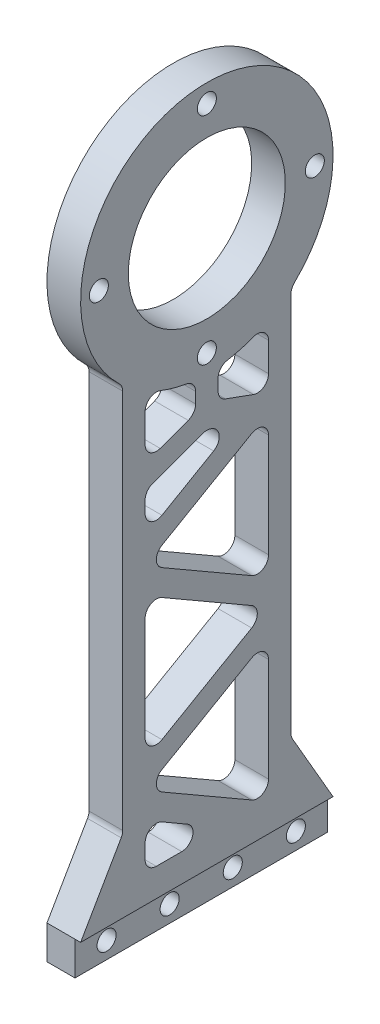
SolidWorks part; units mm, degrees
material "Сплав 2024"
ref_plane "Спереди" through (0, 0, 0) normal (0, 0, 1) x (1, 0, 0)
ref_plane "Сверху" through (0, 0, 0) normal (0, 1, 0) x (1, 0, 0)
ref_plane "Справа" through (0, 0, 0) normal (1, 0, 0) x (0, 0, -1)
sketch "Эскиз1" plane through (0, 0, 0) normal (0, 1, 0) x (1, 0, 0)
  line L1 (0, 0) -> (6, 0)
  line L2 (0, 0) -> (0, -30)
  line L3 (0, -30) -> (6, -30)
  line L4 (6, 0) -> (6, -30)
  dimension "D1" = 6
  dimension "D2" = 30
extrude "Бобышка-Вытянуть1" add sketch "Эскиз1" along normal blind 227
sketch "Эскиз2" plane through (0, 0, 0) normal (-1, 0, 0) x (0, 0, 1)
  line L0 (30, 105) -> (0, 105) construction
  line L3 (15, 227) -> (15, 0) construction
  line L4 (0, 227) -> (30, 227) construction
  line L5 (0, 0) -> (30, 0) construction
  line L6 (30, 0) -> (0, 0) construction
  circle A0 centre (15, 105) radius 22.5
  dimension "D1" = 45
  dimension "D2" = 105
extrude "Бобышка-Вытянуть2" add sketch "Эскиз2" against normal up to surface (6 mm away) up to face at (6, 113.5, 15)
sketch "Эскиз3" plane through (0, 0, 0) normal (-1, 0, 0) x (0, 0, 1)
  circle A0 centre (15, 105) radius 14
  dimension "D1" = 28
extrude "Вырез-Вытянуть1" cut sketch "Эскиз3" against normal through all
sketch "Эскиз4" plane through (6, 0, 0) normal (-1, 0, 0) x (0, 0, 1)
  line L0 (15, 127.5) -> (15, 82.5) construction
  line L1 (15, 227) -> (15, 0) construction
  line L2 (37.5, 105) -> (-7.5, 105) construction
  circle A0 centre (15, 105) radius 19.25 construction
  circle A1 centre (15, 105) radius 22.5 construction
  dimension "D1" = 38.5
hole_wizard "Отверстие с зазором M32" positions "Эскиз6" profile "Эскиз5" hole size "M3" standard "Ansi Metric" end condition through all
sketch "Эскиз6" plane through (6, -25.0247, 7.2629) normal (-1, 0, 0) x (0, 0, 1)
  line L0 (7.7371, 152.5247) -> (7.7371, 107.5247) construction
  line L1 (30.2371, 130.0247) -> (-14.7629, 130.0247) construction
  circle A0 centre (7.7371, 130.0247) radius 19.25 construction
  point P0 (7.7371, 149.2747)
  point P6 (-11.5129, 130.0247)
  point P10 (7.7371, 110.7747)
  point P12 (26.9871, 130.0247)
sketch "Эскиз5" plane through (6, 124.25, 15) normal (0, 1, 0) x (0, 0, -1)
  line L0 (0, 0) -> (0, 6)
  line L1 (0, 6) -> (1.7, 6)
  line L2 (1.7, 6) -> (1.7, 0)
  line L5 (1.7, 0) -> (0, 0)
  line L11 (0, -6.35) -> (0, 107.95) construction
  dimension "Диаметр сквозного отверстия" = 3.4
  dimension "Глубина сквозного отверстия" = 6
sketch "Эскиз8" plane through (6, 0, 0) normal (1, 0, 0) x (0, 0, -1)
  line L0 (-15, 227) -> (-15, 0) construction
  line L1 (-30, 227) -> (0, 227) construction
  line L2 (-30, 0) -> (0, 0) construction
  line L3 (19.447, 105) -> (-49.447, 105) construction
  line L4 (0, 227) -> (0, 121.7705) construction
  line L5 (-26, 145) -> (-4, 145) construction
  line L6 (-26, 145) -> (-26, 65) construction
  line L7 (-26, 65) -> (-4, 65) construction
  line L8 (-4, 145) -> (-4, 65) construction
  line L9 (-26, 145) -> (-4, 65) construction
  line L10 (-26, 65) -> (-4, 145) construction
  point P8 (-15, 105)
  point P9 (-15, 105)
  dimension "D1" = 4
  dimension "D2" = 80
  dimension "D3" = 105
sketch "Эскиз11" plane through (6, 0, 0) normal (1, 0, 0) x (0, 0, -1)
  line L0 (-30, 0) -> (0, 0) construction
  line L1 (-15, 227) -> (-15, 0) construction
  line L2 (-30, 227) -> (0, 227) construction
  line L3 (0, 88.2295) -> (0, 0) construction
  line L4 (-30, 88.2295) -> (-30, 0) construction
  line L5 (-37.5, 3) -> (7.5, 3) construction
  line L6 (-9.375, 6) -> (-9.375, 0) construction
  line L7 (-3.75, 6) -> (-3.75, 0) construction
  line L8 (1.875, 6) -> (1.875, 0) construction
  line L20 (-15, 0) -> (-15, 6) construction
  line L21 (-20.625, 0) -> (-20.625, 6) construction
  line L22 (-26.25, 0) -> (-26.25, 6) construction
  line L23 (-31.875, 0) -> (-31.875, 6) construction
  line L25 (-37.5, 0) -> (7.5, 6) construction
  line L26 (-37.5, 6) -> (7.5, 0) construction
  line L27 (-37.5, 6) -> (7.5, 6) construction
  line L28 (0, 18.9904) -> (7.5, 6)
  line L29 (-30, 18.9904) -> (0, 18.9904)
  line L30 (7.5, 6) -> (7.5, 0)
  line L31 (-37.5, 0) -> (7.5, 0)
  line L32 (-37.5, 6) -> (-37.5, 0)
  line L33 (-37.5, 6) -> (-30, 18.9904)
  point P2 (-15, 3)
  dimension "D1" = 45
  dimension "D2" = 6
  dimension "D3" = 5.625
  dimension "D4" = 5.625
  dimension "D5" = 5.625
  dimension "D6" = 5.625
  dimension "D7" = 120
  dimension "D8" = 5.625
  dimension "D9" = 5.625
  dimension "D10" = 5.625
extrude "Бобышка-Вытянуть3" add sketch "Эскиз11" against normal up to surface (6 mm away) up to face at (0, 124.25, 13.3)
hole_wizard "Отверстие с зазором M31" positions "Эскиз13" profile "Эскиз12" hole size "M3" standard "Ansi Metric" end condition through all
sketch "Эскиз13" plane through (6, 0, 0) normal (1, 0, 0) x (0, 0, -1)
  line L4 (-31.875, 0) -> (-31.875, 6) construction
  line L8 (1.875, 6) -> (1.875, 0) construction
  line L9 (-9.375, 6) -> (-9.375, 0) construction
  line L10 (-20.625, 0) -> (-20.625, 6) construction
  point P16 (-31.875, 3)
  point P20 (-20.625, 3)
  point P24 (-9.375, 3)
  point P28 (1.875, 3)
sketch "Эскиз12" plane through (6, 3, 31.875) normal (0, 1, 0) x (0, 0, -1)
  line L0 (0, 0) -> (0, 6)
  line L1 (0, 6) -> (1.7, 6)
  line L2 (1.7, 6) -> (1.7, 0)
  line L5 (1.7, 0) -> (0, 0)
  line L11 (0, -6.35) -> (0, 107.95) construction
  dimension "Диаметр сквозного отверстия" = 3.4
  dimension "Глубина сквозного отверстия" = 6
sketch "Эскиз14" plane through (6, 0, 0) normal (1, 0, 0) x (0, 0, -1)
  line L5 (-37.5, 0) -> (7.5, 0)
  line L6 (-37.5, 0) -> (-37.5, 6)
  line L7 (-37.5, 6) -> (7.5, 6)
  line L8 (7.5, 0) -> (7.5, 6)
extrude "Вырез-Вытянуть2" cut sketch "Эскиз14" against normal blind 1
sketch "Эскиз15" plane through (6, 0, 0) normal (1, 0, 0) x (0, 0, -1)
  line L0 (0, 227) -> (0, 121.7705) construction
  line L1 (-30, 227) -> (0, 227)
  line L2 (-30, 227) -> (-30, 121.7705)
  line L4 (0, 227) -> (0, 121.7705)
  arc A1 (-30, 121.7705) -> (0, 121.7705) centre (-15, 105) cw
extrude "Вырез-Вытянуть3" cut sketch "Эскиз15" against normal up to surface (6 mm away) up to face at (0, 3, 30.175)
sketch "Эскиз16" [suppressed] plane through (6, 0, 0) normal (1, 0, 0) x (0, 0, -1)
  line L0 (-26, 0) -> (-26, 89.3005) construction
  line L1 (-37.5, 0) -> (7.5, 0) construction
  line L2 (-4, 0) -> (-4, 89.3005) construction
  line L3 (-30, 88.2295) -> (-30, 18.9904) construction
  line L4 (0, 88.2295) -> (0, 18.9904) construction
  line L5 (-30, 80.25) -> (0, 80.25) construction
  line L6 (-26, 80.25) -> (-4, 80.25)
  line L7 (-4, 80.25) -> (-26, 67.5483)
  line L8 (-26, 67.5483) -> (-26, 80.25)
  line L9 (-26, 62.9295) -> (-4, 75.6312)
  line L10 (-4, 75.6312) -> (-4, 50.2278)
  line L11 (-4, 50.2278) -> (-26, 62.9295)
  line L12 (-26, 58.3107) -> (-4, 45.609)
  line L13 (-4, 45.609) -> (-26, 32.9073)
  line L14 (-26, 32.9073) -> (-26, 58.3107)
  line L15 (-26, 28.2885) -> (-4, 40.9902)
  line L16 (-4, 40.9902) -> (-4, 15.5868)
  line L17 (-4, 15.5868) -> (-26, 28.2885)
  line L18 (-26, 23.6697) -> (-4, 10.968)
  line L19 (-4, 10.968) -> (-26, 10.968)
  line L20 (-26, 10.968) -> (-26, 23.6697)
  circle A2 centre (-15, 85.75) radius 1.7 construction
  dimension "D3" = 5.5
  dimension "D1" = 4
  dimension "D2" = 4
  dimension "D4" = 30
  dimension "D5" = 4
  dimension "D6" = 4
  dimension "D7" = 4
  dimension "D8" = 4
  dimension "D9" = 60
  dimension "D10" = 60
  dimension "D11" = 60
extrude "Вырез-Вытянуть4" [suppressed] cut sketch "Эскиз16" against normal through all
fillet "Скругление1" [suppressed] radius 2
chamfer "Фаска1" [suppressed] distance 1 angle 45
sketch "Эскиз17" plane through (6, 0, 0) normal (1, 0, 0) x (0, 0, -1)
  line L0 (-26, 0) -> (-26, 111.7401) construction
  line L1 (-37.5, 0) -> (7.5, 0) construction
  line L2 (-4, 0) -> (-4, 111.7401) construction
  line L3 (-30, 88.2295) -> (-30, 18.9904) construction
  line L4 (0, 88.2295) -> (0, 18.9904) construction
  line L5 (-17, 82.5891) -> (-17, 77.4791)
  line L6 (-13, 82.5891) -> (-13, 77.4791)
  line L7 (-15, 227) -> (-15, 0) construction
  line L8 (-17, 77.4791) -> (-26, 74.2033)
  line L9 (-30, 74.2033) -> (0, 74.2033) construction
  line L10 (-13, 77.4791) -> (-4, 74.2033)
  line L11 (-26, 85.3722) -> (-26, 74.2033)
  line L12 (-30, 77.4791) -> (0, 77.4791) construction
  line L13 (-4, 74.2033) -> (-4, 85.3722)
  line L14 (-26, 69.9466) -> (-15, 73.9503)
  line L15 (-15, 73.9503) -> (-10.073, 72.157)
  line L16 (-4, 71.0444) -> (-4, 45.641)
  line L17 (-26, 69.9466) -> (-26, 62.9615)
  line L18 (-26, 53.7239) -> (-4, 41.0222)
  line L19 (-4, 41.0222) -> (-26, 28.3205)
  line L20 (-26, 28.3205) -> (-26, 53.7239)
  line L21 (-26, 23.7017) -> (-4, 36.4034)
  line L22 (-4, 36.4034) -> (-4, 11)
  line L23 (-4, 11) -> (-26, 23.7017)
  line L24 (-26, 19.0829) -> (-12, 11)
  line L25 (-12, 11) -> (-26, 11)
  line L26 (-26, 11) -> (-26, 19.0829)
  line L27 (-34.6132, 11) -> (4.6132, 11) construction
  line L28 (-30, 18.9904) -> (-37.5, 6) construction
  line L29 (7.5, 6) -> (0, 18.9904) construction
  line L30 (7.5, 6) -> (-37.5, 6) construction
  line L31 (-26, 58.3427) -> (-4, 45.641)
  line L32 (-26, 58.3427) -> (-4, 71.0444) construction
  line L33 (-26, 62.9615) -> (-10.073, 72.157) construction
  line L35 (-26, 58.3427) -> (-4, 71.0444)
  line L36 (-10.073, 72.157) -> (-26, 62.9615)
  circle A0 centre (-15, 105) radius 22.5 construction
  arc A1 (-26, 85.3722) -> (-17, 82.5891) centre (-15, 105) ccw
  arc A2 (-13, 82.5891) -> (-4, 85.3722) centre (-15, 105) ccw
  point P10 (-26, 85.3722)
  point P11 (-4, 85.3722)
  dimension "D1" = 4
  dimension "D2" = 4
  dimension "D3" = 4
  dimension "D4" = 2
  dimension "D5" = 4
  dimension "D6" = 60
  dimension "D7" = 5.11
  dimension "D8" = 110
  dimension "D9" = 30
  dimension "D10" = 4
  dimension "D11" = 60
  dimension "D12" = 4
  dimension "D13" = 4
  dimension "D14" = 5
  dimension "D15" = 60
  dimension "D16" = 4
extrude "Вырез-Вытянуть5" cut sketch "Эскиз17" against normal up to next
fillet "Скругление2" radius 2 28 edges at (3, 74.2033, 4) (3, 77.4791, 13) (3, 74.2033, 26) (3, 82.5891, 13) (3, 85.3722, 4) (3, 82.5891, 17) (3, 85.3722, 26) (3, 62.9615, 26) (3, 69.9466, 26) (3, 72.157, 10.073) (3, 73.9503, 15) (3, 77.4791, 17) (3, 11, 26) (3, 19.0829, 26) (3, 11, 12) (3, 11, 4) (3, 36.4034, 4) (3, 23.7017, 26) (3, 28.3205, 26) (3, 53.7239, 26) (3, 41.0222, 4) (3, 45.641, 4) (3, 58.3427, 26) (3, 71.0444, 4) (3, 18.9904, 0) (3, 18.9904, 30) (3, 88.2295, 30) (3, 88.2295, 0)
equation "\"D4@Эскиз11\"=\"D3@Эскиз11\""
equation "\"D5@Эскиз11\"=\"D3@Эскиз11\""
equation "\"D6@Эскиз11\"=\"D4@Эскиз11\""
equation "\"D3@Эскиз11\"=\"D1@Эскиз11\" / 8"
equation "\"D10@Эскиз16\"=\"D4@Эскиз16\"*2"
equation "\"D9@Эскиз16\"=\"D10@Эскиз16\""
equation "\"D11@Эскиз16\"=\"D10@Эскиз16\""
equation "\"D8@Эскиз11\"=\"D3@Эскиз11\""
equation "\"D9@Эскиз11\"=\"D3@Эскиз11\""
equation "\"D10@Эскиз11\"=\"D3@Эскиз11\""
